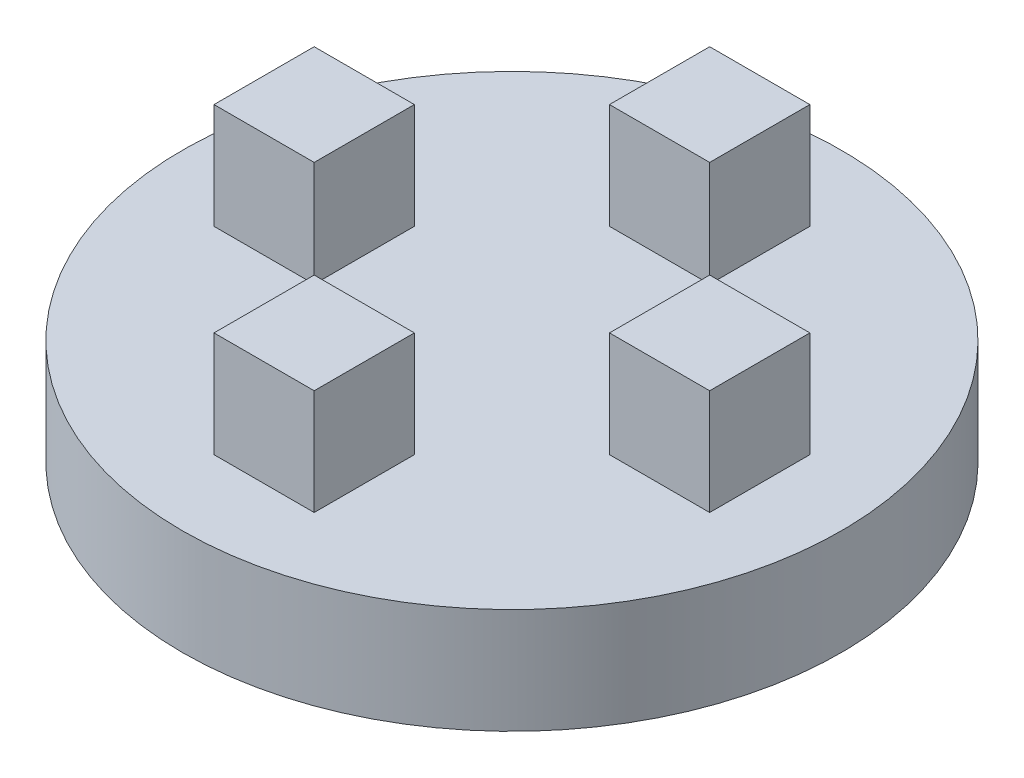
SolidWorks part; units mm, degrees
ref_plane "Front Plane" through (0, 0, 0) normal (0, 0, 1) x (1, 0, 0)
ref_plane "Top Plane" through (0, 0, 0) normal (0, 1, 0) x (1, 0, 0)
ref_plane "Right Plane" through (0, 0, 0) normal (1, 0, 0) x (0, 0, -1)
sketch "Sketch1" plane through (0, 0, 0) normal (0, 1, 0) x (1, 0, 0)
  circle A0 centre (0, 0) radius 12.5
  dimension "D1" = 25
extrude "Boss-Extrude1" add sketch "Sketch1" along normal mid plane 4
sketch "Sketch2" plane through (0, 2, 0) normal (0, 1, 0) x (1, 0, 0)
  line L1 (-2, 9.5) -> (2, 9.5) construction
  line L2 (-2, 9.5) -> (-2, 5.5) construction
  line L3 (-2, 5.5) -> (2, 5.5) construction
  line L4 (2, 9.5) -> (2, 5.5) construction
  line L5 (-1.9, 9.4) -> (-1.9, 5.6)
  line L6 (-1.9, 5.6) -> (1.9, 5.6)
  line L7 (1.9, 9.4) -> (1.9, 5.6)
  line L8 (-1.9, 9.4) -> (1.9, 9.4)
  line L9 (9.4, 1.9) -> (5.6, 1.9)
  line L10 (5.6, 1.9) -> (5.6, -1.9)
  line L11 (9.4, -1.9) -> (5.6, -1.9)
  line L12 (9.4, 1.9) -> (9.4, -1.9)
  line L13 (1.9, -9.4) -> (1.9, -5.6)
  line L14 (1.9, -5.6) -> (-1.9, -5.6)
  line L15 (-1.9, -9.4) -> (-1.9, -5.6)
  line L16 (1.9, -9.4) -> (-1.9, -9.4)
  line L17 (-9.4, -1.9) -> (-5.6, -1.9)
  line L18 (-5.6, -1.9) -> (-5.6, 1.9)
  line L19 (-9.4, 1.9) -> (-5.6, 1.9)
  line L20 (-9.4, -1.9) -> (-9.4, 1.9)
  point P4 (0, 5.5)
  point P25 (0, 0)
  dimension "D1" = 5.5
  dimension "D2" = 4
  dimension "D3" = 4
  dimension "D4" = 0.1
  dimension "D5" = 4
extrude "Boss-Extrude3" add sketch "Sketch2" along normal blind 4
sketch "Sketch3" plane through (0, -2, 0) normal (0, -1, 0) x (1, 0, 0)
  circle A0 centre (0, 0) radius 5
  dimension "D1" = 10
extrude "Boss-Extrude4" add sketch "Sketch3" along normal blind 1
sketch "Sketch4" plane through (0, -3, 0) normal (0, -1, 0) x (1, 0, 0)
  line L1 (0, -3.675) -> (3.1826, -1.8375)
  line L2 (3.1826, -1.8375) -> (3.1826, 1.8375)
  line L3 (3.1826, 1.8375) -> (0, 3.675)
  line L4 (0, 3.675) -> (-3.1826, 1.8375)
  line L5 (-3.1826, 1.8375) -> (-3.1826, -1.8375)
  line L6 (-3.1826, -1.8375) -> (0, -3.675)
  circle A0 centre (0, 0) radius 3.675 construction
  circle A1 centre (0, 0) radius 3.1826 construction
  dimension "D1" = 7.35
extrude "Boss-Extrude5" add sketch "Sketch4" along normal blind 5
